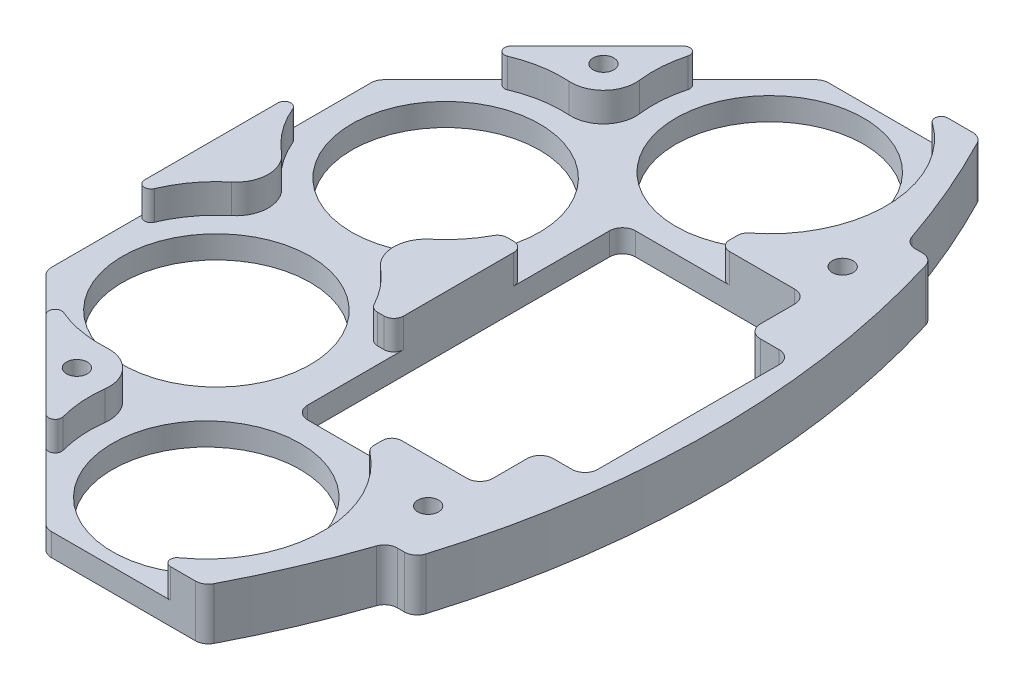
SolidWorks part; units mm, degrees
material "ABS"
ref_plane "Front Plane" through (0, 0, 0) normal (0, 0, 1) x (1, 0, 0)
ref_plane "Top Plane" through (0, 0, 0) normal (0, 1, 0) x (1, 0, 0)
ref_plane "Right Plane" through (0, 0, 0) normal (1, 0, 0) x (0, 0, -1)
sketch "Sketch1" plane through (0, 0, 0) normal (0, 1, 0) x (1, 0, 0)
  line L0 (0, 0) -> (98.9949, 98.9949) construction
  line L1 (98.9949, -98.9949) -> (0, 0) construction
  line L2 (0, 0) -> (140, 0) construction
  line L3 (34.6482, 64.3467) -> (84.1457, 113.8442) construction
  line L4 (34.6482, 64.3467) -> (64.3467, 34.6482) construction
  line L5 (84.1457, 113.8442) -> (113.8442, 84.1457) construction
  line L6 (64.3467, 34.6482) -> (113.8442, 84.1457) construction
  line L7 (34.6482, 64.3467) -> (113.8442, 84.1457) construction
  line L8 (84.1457, 113.8442) -> (64.3467, 34.6482) construction
  line L9 (64.3467, -34.6482) -> (113.8442, -84.1457) construction
  line L10 (64.3467, -34.6482) -> (34.6482, -64.3467) construction
  line L11 (113.8442, -84.1457) -> (84.1457, -113.8442) construction
  line L12 (34.6482, -64.3467) -> (84.1457, -113.8442) construction
  line L13 (64.3467, -34.6482) -> (84.1457, -113.8442) construction
  line L14 (113.8442, -84.1457) -> (34.6482, -64.3467) construction
  line L15 (50, 25.9584) -> (84.0416, 60)
  line L16 (50, 25.9584) -> (50, 0)
  line L17 (50, 0) -> (132, 0)
  line L18 (95.4594, 65.7609) -> (91.2168, 61.5183) construction
  line L19 (95.4594, 65.7609) -> (80.6102, 80.6102) construction
  line L20 (84.0416, 60) -> (117.5755, 60)
  line L22 (91.2168, 61.5183) -> (76.3675, 76.3675) construction
  line L23 (80.6102, 80.6102) -> (76.3675, 76.3675) construction
  arc A0 (98.9949, 98.9949) -> (98.9949, -98.9949) centre (0, 0) cw construction
  arc A5 (117.5755, 60) -> (132, 0) centre (0, 0) cw
  point P6 (74.2462, 74.2462)
  point P7 (74.2462, -74.2462)
  dimension "D5" = 6
  dimension "D8" = 8
  dimension "D1" = 90
  dimension "D2" = 140
  dimension "D3" = 42
  dimension "D4" = 70
  dimension "D6" = 17
  dimension "D7" = 60
  dimension "D9" = 108
  dimension "D11" = 50
extrude "Boss-Extrude1" add sketch "Sketch1" along normal blind 8
sketch "Sketch2" plane through (0, 8, 0) normal (0, 1, 0) x (1, 0, 0)
  line L1 (55, 41.8225) -> (55, 0) construction
  line L2 (91, 0) -> (119, 0) construction
  line L3 (91, 0) -> (91, 25) construction
  line L4 (91, 25) -> (119, 25) construction
  line L5 (119, 0) -> (119, 25) construction
  line L6 (0, 0) -> (135.2492, 0) construction
  line L8 (84.0416, 60) -> (50, 25.9584) construction
  circle A0 centre (97.2395, 43.4994) radius 18
  circle A1 centre (73, 17.7) radius 18
  arc A2 (112.5444, 54.9649) -> (125.2492, 0) centre (0, 0) cw construction
  line M10 (50, 0) -> (132, 0)
  dimension "D1" = 36
  dimension "D4" = 91
  dimension "D2" = 25
  dimension "D3" = 28
  dimension "D5" = 55
  dimension "D6" = 35.4
  dimension "D8" = 21
extrude "Cut-Extrude4" cut sketch "Sketch2" against normal blind 4.5 contours A1 A0 M10 | A1 A0 | A0 A1 region at (97.2708, 8, -43.5327) region at (85.1197, 8, -30.5997) region at (72.9687, 8, -17.6897)
sketch "Sketch12" plane through (0, 3.5, 0) normal (0, 1, 0) x (1, 0, 0)
  circle A0 centre (97.2395, 43.4994) radius 14.5
  circle A1 centre (73, 17.7) radius 14.5
  dimension "D1" = 29
extrude "Cut-Extrude14" cut sketch "Sketch12" against normal up to next
mirror "Mirror2" about plane through (0, 0, 0) normal (0, 0, 1) of "Cut-Extrude14", "Cut-Extrude4", "Boss-Extrude1"
fillet "Fillet3" radius 5 6 edges at (87.5048, 5.75, 28.3588) (82.7347, 5.75, 32.8405) (76.2726, 5.75, 0) (69.7274, 5.75, 0) (87.5048, 5.75, -28.3588) (82.7347, 5.75, -32.8405)
fillet "Fillet5" radius 1 4 edges at (104.4318, 5.75, 60) (90.0472, 5.75, 60) (104.4318, 5.75, -60) (90.0472, 5.75, -60)
sketch "Sketch3" plane through (0, 8, 0) normal (0, 1, 0) x (1, 0, 0)
  line L1 (92.7, 25.3) -> (121.3, 25.3)
  line L2 (92.7, 25.3) -> (92.7, -25.3)
  line L3 (92.7, -25.3) -> (121.3, -25.3)
  line L4 (121.3, 25.3) -> (121.3, -25.3)
  arc A1 (120.4495, 29.0808) -> (119.4086, -33.0962) centre (0, 0) cw construction
  dimension "D3" = 92.7
  dimension "D1" = 28.6
  dimension "D2" = 50.6
extrude "Cut-Extrude5" cut sketch "Sketch3" against normal up to next
sketch "Sketch6" plane through (0, 8, 0) normal (0, 1, 0) x (1, 0, 0)
  line L0 (121.3, -25.3) -> (121.3, 25.3) construction
  line L1 (121.3, 16) -> (128.2, 16)
  line L2 (121.3, 16) -> (121.3, -16)
  line L3 (121.3, -16) -> (128.2, -16)
  line L4 (128.2, 16) -> (128.2, -16)
  line L6 (92.7, 25.3) -> (92.7, -25.3) construction
  line L7 (92.7, 24.4472) -> (92.7, -24.4472) construction
  point P6 (92.7, 0)
  dimension "D1" = 32
  dimension "D2" = 16
  dimension "D3" = 35.5
extrude "Cut-Extrude8" cut sketch "Sketch6" against normal up to next
fillet "Fillet4" radius 2 8 edges at (121.3, 4, 25.3) (92.7, 1.75, 25.3) (121.3, 4, -25.3) (92.7, 1.75, -25.3) (121.3, 4, 16) (128.2, 4, 16) (121.3, 4, -16) (128.2, 4, -16)
sketch "Sketch8" plane through (0, 8, 0) normal (0, 1, 0) x (1, 0, 0)
  line L0 (117.5755, 60) -> (108.2272, 60) construction
  line L1 (117.5755, -60) -> (108.2272, -60) construction
  line L2 (121.7935, 40) -> (125.7935, 40)
  line L3 (121.7935, -40) -> (125.7935, -40)
  arc A0 (113.2857, 60) -> (121.7935, 40) centre (0, 0) cw
  arc A1 (125.7935, -40) -> (125.7935, 40) centre (0, 0) ccw
  arc A2 (117.5755, -60) -> (117.5755, 60) centre (0, 0) ccw construction
  arc A3 (113.2857, -60) -> (121.7935, -40) centre (0, 0) ccw
  dimension "D1" = 4
  dimension "D2" = 80
  dimension "D3" = 40
extrude "Cut-Extrude10" cut sketch "Sketch8" against normal through all and the other way through all flip side to cut
sketch "Sketch9" plane through (0, 0, 0) normal (0, -1, 0) x (1, 0, 0)
  circle A0 centre (120, 32) radius 1.6
  circle A1 centre (120, -32) radius 1.6
  arc A2 (125.7935, -40) -> (125.7935, 40) centre (0, 0) ccw construction
  dimension "D1" = 120
  dimension "D2" = 3.2
  dimension "D3" = 32
  dimension "D4" = 32
extrude "Cut-Extrude11" cut sketch "Sketch9" against normal up to next
sketch "Sketch10" plane through (0, 8, 0) normal (0, 1, 0) x (1, 0, 0)
  circle A0 centre (74.4159, 40.6564) radius 1.6
  circle A1 centre (74.4159, -40.6564) radius 1.6
  dimension "D1" = 3.2
extrude "Cut-Extrude12" cut sketch "Sketch10" against normal up to next
sketch "Sketch11" plane through (0, 8, 0) normal (0, 1, 0) x (1, 0, 0)
  line L0 (89.2699, 10) -> (89.2699, 28.8509)
  line L1 (107.7, 28.8509) -> (89.2699, 28.8509)
  line L2 (107.7, 28.8509) -> (107.7, -28.8509)
  line L3 (107.7, -28.8509) -> (89.2699, -28.8509)
  line L4 (89.2699, 10) -> (92.7, 10)
  line L5 (92.7, 23.3) -> (92.7, -23.3) construction
  line L6 (92.7, 10) -> (92.7, -10)
  line L7 (92.7, -10) -> (89.2699, -10)
  line L8 (89.2699, -10) -> (89.2699, -28.8509)
  arc A1 (107.6489, -58.1842) -> (96.1314, -25.5335) centre (97.2395, -43.4994) ccw construction
  arc A2 (96.1314, 25.5335) -> (107.6489, 58.1842) centre (97.2395, 43.4994) ccw construction
  arc A4 (90.862, -19.9249) -> (84.4942, -3.8478) centre (73, -17.7) ccw construction
  arc A5 (84.4942, 3.8478) -> (90.862, 19.9249) centre (73, 17.7) ccw construction
  dimension "D1" = 20
  dimension "D2" = 15
extrude "Cut-Extrude13" cut sketch "Sketch11" against normal up to surface (4.5 mm away) up to face at (87.594, 3.5, 0)
fillet "Fillet8" radius 1.5 8 edges at (89.2699, 5.75, -10) (92.7, 5.75, -10) (107.7, 5.75, 28.8509) (107.7, 5.75, 25.3) (89.2699, 5.75, 10) (92.7, 5.75, 10) (107.7, 5.75, -28.8509) (107.7, 5.75, -25.3)
sketch "Sketch13" plane through (0, 8, 0) normal (0, 1, 0) x (1, 0, 0)
  line L0 (84.0416, 60) -> (88.9914, 60)
  line L1 (86.2517, 60) -> (84.0416, 60) construction
  line L2 (88.9914, 60) -> (54.5, 25.5086)
  line L3 (54.5, 25.5086) -> (54.5, -25.5086)
  line L4 (54.5, -25.5086) -> (88.9914, -60)
  line L5 (86.2517, -60) -> (84.0416, -60) construction
  line L6 (88.9914, -60) -> (84.0416, -60)
  line L7 (84.0416, -60) -> (50, -25.9584)
  line L8 (50, -25.9584) -> (50, 25.9584)
  line L9 (50, 25.9584) -> (84.0416, 60)
  dimension "D1" = 3.5
  dimension "D2" = 4.5
extrude "Cut-Extrude15" cut sketch "Sketch13" against normal up to next
sketch "Sketch15" plane through (0, 8, 0) normal (0, 1, 0) x (1, 0, 0)
  line L0 (81.886, 52.8946) -> (78.2037, 49.2123)
  line L1 (81.886, 52.8946) -> (86.2967, 48.4839)
  line L2 (79.8754, 48.2417) -> (82.965, 45.1522)
  line L3 (86.2967, 48.4839) -> (82.965, 45.1522)
  line L4 (54.5, 25.5086) -> (81.886, 52.8946) construction
  line L6 (64.9021, 35.9107) -> (54.5, 25.5086)
  line L7 (54.5, 25.5086) -> (54.5, 10.3007)
  line L8 (54.5, -25.5086) -> (54.5, 25.5086) construction
  line L10 (56.4211, 10.6901) -> (56.4211, 24.7052)
  line L11 (56.4211, 24.7052) -> (65.9982, 34.2824)
  arc A1 (74.1081, 35.6659) -> (61.5058, 3.8478) centre (73, 17.7) ccw construction
  arc A4 (78.2037, 49.2123) -> (79.8754, 48.2417) centre (78.9108, 48.5052) cw
  arc A5 (81.886, 52.8946) -> (79.3775, 41.2744) centre (97.2395, 43.4994) ccw construction
  arc A6 (64.9021, 35.9107) -> (65.9982, 34.2824) centre (65.6092, 35.2036) ccw
  arc A7 (54.5, 10.3007) -> (56.4211, 10.6901) centre (55.5, 10.3007) cw
  dimension "D2" = 1
extrude "Cut-Extrude17" cut sketch "Sketch15" against normal up to surface (4.5 mm away) up to face at (92.471, 3.5, 0)
mirror "Mirror3" about plane through (0, 0, 0) normal (0, 0, 1) of "Cut-Extrude17"
fillet "Fillet9" radius 2 10 edges at (125.7935, 4, -40) (121.7935, 4, -40) (113.2857, 4, -60) (88.9914, 1.75, -60) (54.5, 1.75, -25.5086) (54.5, 1.75, 25.5086) (125.7935, 4, 40) (121.7935, 4, 40) (88.9914, 1.75, 60) (113.2857, 4, 60)
sketch "Sketch14" plane through (0, 0, 0) normal (0, -1, 0) x (1, 0, 0)
  circle A0 centre (74.4159, 40.6564) radius 3.1
  circle A1 centre (120, 32) radius 3.1
  circle A2 centre (120, -32) radius 3.1
  circle A3 centre (74.4159, -40.6564) radius 3.1
  dimension "D1" = 6.2
extrude "Cut-Extrude16" cut sketch "Sketch14" against normal blind 3
chamfer "Chamfer1" distance 1.5 angle 45 4 edges at (74.4159, 3, 39.0564) (120, 3, -33.6) (74.4159, 3, -42.2564) (120, 3, 30.4)
